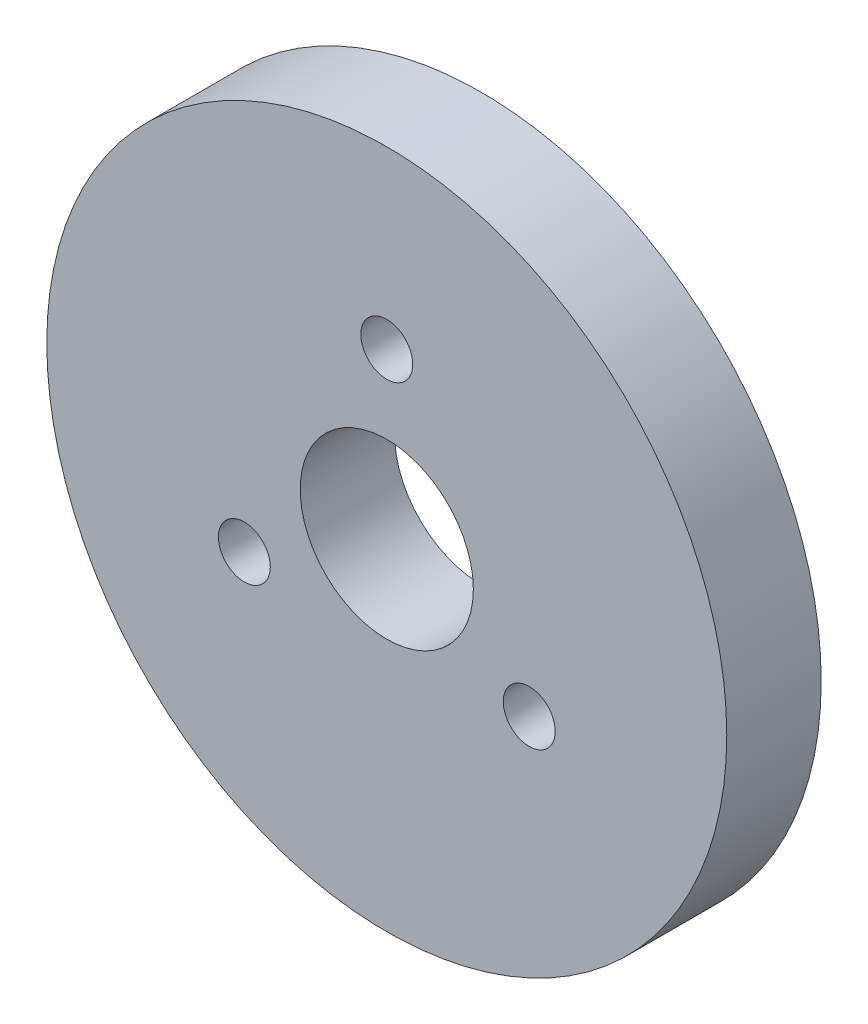
SolidWorks part; units mm, degrees
ref_plane "Front Plane" through (0, 0, 0) normal (0, 0, 1) x (1, 0, 0)
ref_plane "Top Plane" through (0, 0, 0) normal (0, 1, 0) x (1, 0, 0)
ref_plane "Right Plane" through (0, 0, 0) normal (1, 0, 0) x (0, 0, -1)
sketch "Sketch1" plane through (0, 0, 0) normal (0, 0, 1) x (1, 0, 0)
  circle A0 centre (0, 0) radius 21.6
  circle A1 centre (0, 0) radius 5.5
  dimension "D1" = 43.2
  dimension "D2" = 11
extrude "Boss-Extrude1" add sketch "Sketch1" along normal blind 6
sketch "Sketch2" plane through (0, 0, 6) normal (0, 0, 1) x (1, 0, 0)
  line L0 (0, 0) -> (0, 50000) construction
  line L1 (0, 0) -> (50000, 0) construction
  circle A0 centre (0, 10.45) radius 1.65
  circle A1 centre (0, 0) radius 5.5 construction
  circle A2 centre (9.05, -5.225) radius 1.65
  circle A3 centre (-9.05, -5.225) radius 1.65
  point P16 (0, 0)
  dimension "D1" = 3.3
  dimension "D2" = 10.45
  dimension "D3" = 3
extrude "Cut-Extrude1" cut sketch "Sketch2" against normal blind 3
